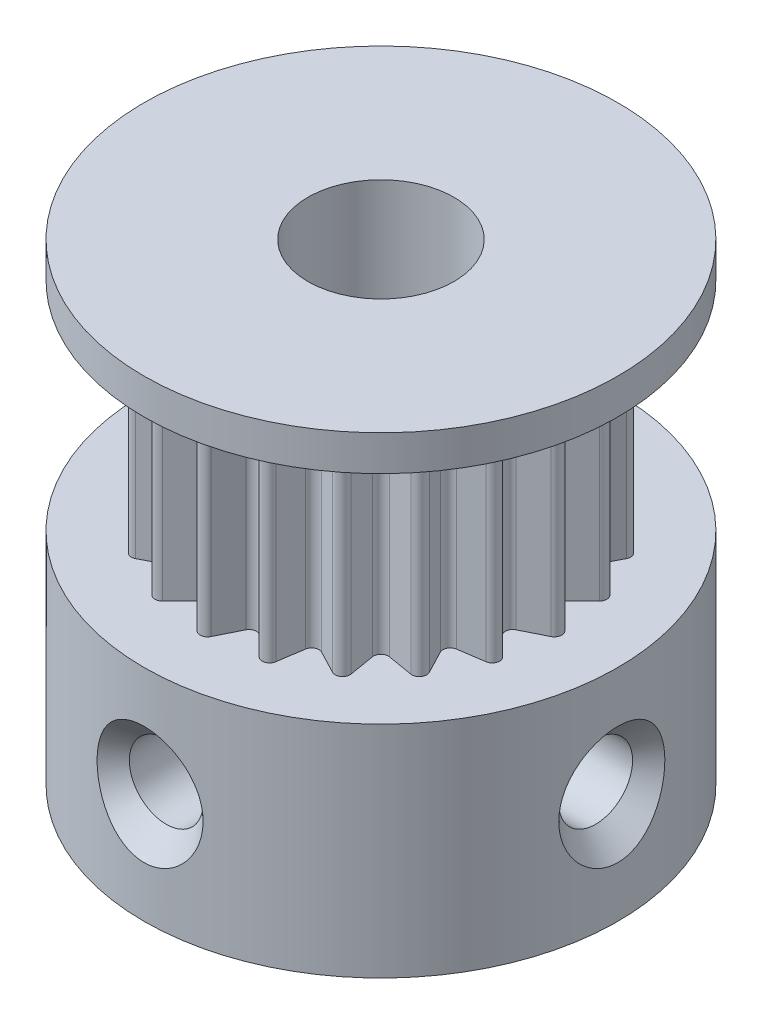
SolidWorks part; units mm, degrees
ref_plane "Front Plane" through (0, 0, 0) normal (0, 0, 1) x (1, 0, 0)
ref_plane "Top Plane" through (0, 0, 0) normal (0, 1, 0) x (1, 0, 0)
ref_plane "Right Plane" through (0, 0, 0) normal (1, 0, 0) x (0, 0, -1)
sketch "Sketch1" plane through (0, 0, 0) normal (0, 1, 0) x (1, 0, 0)
  circle A0 centre (0, 0) radius 8.025
  dimension "D1" = 16.05
extrude "Boss-Extrude1" add sketch "Sketch1" along normal blind 16
sketch "Sketch2" plane through (0, 16, 0) normal (0, 1, 0) x (1, 0, 0)
  line L0 (0.2238, 5.9865) -> (0.6171, 5.1973)
  line L1 (1.0192, 5.1336) -> (1.6371, 5.7627)
  line L2 (0, 0) -> (0, 6.125) construction
  line L3 (0.8408, 5.3088) -> (0.9582, 6.0496) construction
  line L4 (1.8927, 5.8252) -> (0, 0) construction
  line L5 (2.0627, 5.6244) -> (2.1929, 4.7522)
  line L6 (2.5557, 4.5674) -> (3.3378, 4.9747)
  line L7 (3.6998, 4.7117) -> (3.5541, 3.842)
  line L8 (3.842, 3.5541) -> (4.7117, 3.6998)
  line L9 (4.9747, 3.3378) -> (4.5674, 2.5557)
  line L10 (4.7522, 2.1929) -> (5.6244, 2.0627)
  line L11 (5.7627, 1.6371) -> (5.1336, 1.0192)
  line L12 (5.1973, 0.6171) -> (5.9865, 0.2238)
  line L13 (5.9865, -0.2238) -> (5.1973, -0.6171)
  line L14 (5.1336, -1.0192) -> (5.7627, -1.6371)
  line L15 (5.6244, -2.0627) -> (4.7522, -2.1929)
  line L16 (4.5674, -2.5557) -> (4.9747, -3.3378)
  line L17 (4.7117, -3.6998) -> (3.842, -3.5541)
  line L18 (3.5541, -3.842) -> (3.6998, -4.7117)
  line L19 (3.3378, -4.9747) -> (2.5557, -4.5674)
  line L20 (2.1929, -4.7522) -> (2.0627, -5.6244)
  line L21 (1.6371, -5.7627) -> (1.0192, -5.1336)
  line L22 (0.6171, -5.1973) -> (0.2238, -5.9865)
  line L23 (-0.2238, -5.9865) -> (-0.6171, -5.1973)
  line L24 (-1.0192, -5.1336) -> (-1.6371, -5.7627)
  line L25 (-2.0627, -5.6244) -> (-2.1929, -4.7522)
  line L26 (-2.5557, -4.5674) -> (-3.3378, -4.9747)
  line L27 (-3.6998, -4.7117) -> (-3.5541, -3.842)
  line L28 (-3.842, -3.5541) -> (-4.7117, -3.6998)
  line L29 (-4.9747, -3.3378) -> (-4.5674, -2.5557)
  line L30 (-4.7522, -2.1929) -> (-5.6244, -2.0627)
  line L31 (-5.7627, -1.6371) -> (-5.1336, -1.0192)
  line L32 (-5.1973, -0.6171) -> (-5.9865, -0.2238)
  line L33 (-5.9865, 0.2238) -> (-5.1973, 0.6171)
  line L34 (-5.1336, 1.0192) -> (-5.7627, 1.6371)
  line L35 (-5.6244, 2.0627) -> (-4.7522, 2.1929)
  line L36 (-4.5674, 2.5557) -> (-4.9747, 3.3378)
  line L37 (-4.7117, 3.6998) -> (-3.842, 3.5541)
  line L38 (-3.5541, 3.842) -> (-3.6998, 4.7117)
  line L39 (-3.3378, 4.9747) -> (-2.5557, 4.5674)
  line L40 (-2.1929, 4.7522) -> (-2.0627, 5.6244)
  line L41 (-1.6371, 5.7627) -> (-1.0192, 5.1336)
  line L42 (-0.6171, 5.1973) -> (-0.2238, 5.9865)
  line L43 (0, 0) -> (1.0192, 5.1336) construction
  line L44 (0, 0) -> (2.5557, 4.5674) construction
  circle A0 centre (0, 0) radius 6.125 construction
  arc A1 (0.2238, 5.9865) -> (0, 6.125) centre (0, 5.875) ccw
  arc A3 (0.6171, 5.1973) -> (1.0192, 5.1336) centre (0.8408, 5.3088) ccw
  arc A4 (1.6371, 5.7627) -> (1.8927, 5.8252) centre (1.8155, 5.5875) cw
  arc A5 (2.0627, 5.6244) -> (1.8927, 5.8252) centre (1.8155, 5.5875) ccw
  arc A6 (2.1929, 4.7522) -> (2.5557, 4.5674) centre (2.4402, 4.7892) ccw
  arc A7 (3.3378, 4.9747) -> (3.6002, 4.9552) centre (3.4532, 4.753) cw
  arc A8 (3.6998, 4.7117) -> (3.6002, 4.9552) centre (3.4532, 4.753) ccw
  arc A9 (3.5541, 3.842) -> (3.842, 3.5541) centre (3.8007, 3.8007) ccw
  arc A10 (4.7117, 3.6998) -> (4.9552, 3.6002) centre (4.753, 3.4532) cw
  arc A11 (4.9747, 3.3378) -> (4.9552, 3.6002) centre (4.753, 3.4532) ccw
  arc A12 (4.5674, 2.5557) -> (4.7522, 2.1929) centre (4.7892, 2.4402) ccw
  arc A13 (5.6244, 2.0627) -> (5.8252, 1.8927) centre (5.5875, 1.8155) cw
  arc A14 (5.7627, 1.6371) -> (5.8252, 1.8927) centre (5.5875, 1.8155) ccw
  arc A15 (5.1336, 1.0192) -> (5.1973, 0.6171) centre (5.3088, 0.8408) ccw
  arc A16 (5.9865, 0.2238) -> (6.125, 0) centre (5.875, 0) cw
  arc A17 (5.9865, -0.2238) -> (6.125, 0) centre (5.875, 0) ccw
  arc A18 (5.1973, -0.6171) -> (5.1336, -1.0192) centre (5.3088, -0.8408) ccw
  arc A19 (5.7627, -1.6371) -> (5.8252, -1.8927) centre (5.5875, -1.8155) cw
  arc A20 (5.6244, -2.0627) -> (5.8252, -1.8927) centre (5.5875, -1.8155) ccw
  arc A21 (4.7522, -2.1929) -> (4.5674, -2.5557) centre (4.7892, -2.4402) ccw
  arc A22 (4.9747, -3.3378) -> (4.9552, -3.6002) centre (4.753, -3.4532) cw
  arc A23 (4.7117, -3.6998) -> (4.9552, -3.6002) centre (4.753, -3.4532) ccw
  arc A24 (3.842, -3.5541) -> (3.5541, -3.842) centre (3.8007, -3.8007) ccw
  arc A25 (3.6998, -4.7117) -> (3.6002, -4.9552) centre (3.4532, -4.753) cw
  arc A26 (3.3378, -4.9747) -> (3.6002, -4.9552) centre (3.4532, -4.753) ccw
  arc A27 (2.5557, -4.5674) -> (2.1929, -4.7522) centre (2.4402, -4.7892) ccw
  arc A28 (2.0627, -5.6244) -> (1.8927, -5.8252) centre (1.8155, -5.5875) cw
  arc A29 (1.6371, -5.7627) -> (1.8927, -5.8252) centre (1.8155, -5.5875) ccw
  arc A30 (1.0192, -5.1336) -> (0.6171, -5.1973) centre (0.8408, -5.3088) ccw
  arc A31 (0.2238, -5.9865) -> (0, -6.125) centre (0, -5.875) cw
  arc A32 (-0.2238, -5.9865) -> (0, -6.125) centre (0, -5.875) ccw
  arc A33 (-0.6171, -5.1973) -> (-1.0192, -5.1336) centre (-0.8408, -5.3088) ccw
  arc A34 (-1.6371, -5.7627) -> (-1.8927, -5.8252) centre (-1.8155, -5.5875) cw
  arc A35 (-2.0627, -5.6244) -> (-1.8927, -5.8252) centre (-1.8155, -5.5875) ccw
  arc A36 (-2.1929, -4.7522) -> (-2.5557, -4.5674) centre (-2.4402, -4.7892) ccw
  arc A37 (-3.3378, -4.9747) -> (-3.6002, -4.9552) centre (-3.4532, -4.753) cw
  arc A38 (-3.6998, -4.7117) -> (-3.6002, -4.9552) centre (-3.4532, -4.753) ccw
  arc A39 (-3.5541, -3.842) -> (-3.842, -3.5541) centre (-3.8007, -3.8007) ccw
  arc A40 (-4.7117, -3.6998) -> (-4.9552, -3.6002) centre (-4.753, -3.4532) cw
  arc A41 (-4.9747, -3.3378) -> (-4.9552, -3.6002) centre (-4.753, -3.4532) ccw
  arc A42 (-4.5674, -2.5557) -> (-4.7522, -2.1929) centre (-4.7892, -2.4402) ccw
  arc A43 (-5.6244, -2.0627) -> (-5.8252, -1.8927) centre (-5.5875, -1.8155) cw
  arc A44 (-5.7627, -1.6371) -> (-5.8252, -1.8927) centre (-5.5875, -1.8155) ccw
  arc A45 (-5.1336, -1.0192) -> (-5.1973, -0.6171) centre (-5.3088, -0.8408) ccw
  arc A46 (-5.9865, -0.2238) -> (-6.125, 0) centre (-5.875, 0) cw
  arc A47 (-5.9865, 0.2238) -> (-6.125, 0) centre (-5.875, 0) ccw
  arc A48 (-5.1973, 0.6171) -> (-5.1336, 1.0192) centre (-5.3088, 0.8408) ccw
  arc A49 (-5.7627, 1.6371) -> (-5.8252, 1.8927) centre (-5.5875, 1.8155) cw
  arc A50 (-5.6244, 2.0627) -> (-5.8252, 1.8927) centre (-5.5875, 1.8155) ccw
  arc A51 (-4.7522, 2.1929) -> (-4.5674, 2.5557) centre (-4.7892, 2.4402) ccw
  arc A52 (-4.9747, 3.3378) -> (-4.9552, 3.6002) centre (-4.753, 3.4532) cw
  arc A53 (-4.7117, 3.6998) -> (-4.9552, 3.6002) centre (-4.753, 3.4532) ccw
  arc A54 (-3.842, 3.5541) -> (-3.5541, 3.842) centre (-3.8007, 3.8007) ccw
  arc A55 (-3.6998, 4.7117) -> (-3.6002, 4.9552) centre (-3.4532, 4.753) cw
  arc A56 (-3.3378, 4.9747) -> (-3.6002, 4.9552) centre (-3.4532, 4.753) ccw
  arc A57 (-2.5557, 4.5674) -> (-2.1929, 4.7522) centre (-2.4402, 4.7892) ccw
  arc A58 (-2.0627, 5.6244) -> (-1.8927, 5.8252) centre (-1.8155, 5.5875) cw
  arc A59 (-1.6371, 5.7627) -> (-1.8927, 5.8252) centre (-1.8155, 5.5875) ccw
  arc A60 (-1.0192, 5.1336) -> (-0.6171, 5.1973) centre (-0.8408, 5.3088) ccw
  arc A61 (-0.2238, 5.9865) -> (0, 6.125) centre (0, 5.875) cw
  circle A62 centre (0, 0) radius 8.025 construction
  circle A63 centre (0, 0) radius 8.025
  circle M4 centre (0, 0) radius 8.025
  dimension "D1" = 12.25
  dimension "D2" = 0.5
  dimension "D3" = 1
  dimension "D5" = 0.25
  dimension "D4" = 18
  dimension "D7" = 18
  dimension "D6" = 20
extrude "Cut-Extrude1" cut sketch "Sketch2" against normal blind 7.35 from offset 1.2 contours L42 A61 A1 L0 A3 L1 A4 A5 L5 A6 L6 A7 A8 L7 A9 L8 A10 A11 L9 A12 L10 A13 A14 L11 A15 L12 A16 A17 L13 A18 L14 A19 A20 L15 A21 L16 A22 A23 L17 A24 L18 A25 A26 L19 A27 L20 A28 A29 L21 M4 region at (-7.798, 16, 0) offset against normal yes
sketch "Sketch3" plane through (0, 16, 0) normal (0, 1, 0) x (1, 0, 0)
  circle A0 centre (0, 0) radius 2.475
  dimension "D1" = 4.95
extrude "Cut-Extrude2" cut sketch "Sketch3" against normal through all
hole_wizard "M3x0.5 Tapped Hole1" positions "3DSketch2" profile "Sketch4" tap size "M3x0.5" standard "ANSI Metric" end condition up to next
sketch3d "3DSketch2"
  line L0 (0, 0, 0) -> (0, 7.45, 0) construction
  line L1 (0, 7.45, 0) -> (0, 0, 0) construction
  line L2 (0, 3.725, 0) -> (0, 3.725, 8.025) construction
  point P9 (0, 3.725, 8.025)
sketch "Sketch4" plane through (0, 3.725, 8.025) normal (1, 0, 0) x (0, -1, 0)
  line L0 (0, 0) -> (0, 5.55)
  line L1 (0, 5.55) -> (1.25, 5.55)
  line L2 (1.25, 5.55) -> (1.25, 0.75)
  line L3 (1.25, 0.75) -> (2, 0)
  line L5 (2, 0) -> (0, 0)
  line L6 (-1.25, 0.75) -> (-2, 0) construction
  line L11 (0, -6.35) -> (0, 107.95) construction
  dimension "Thru Tap Drill Dia." = 2.5
  dimension "Thru Tap Drill Depth" = 5.55
  dimension "Near C'Sink Dia." = 4
  dimension "Near C'Sink Angle" = 90
cosmetic thread "Hole Thread1" parameters "D2"=3
pattern_circular "CirPattern1" count 2 over 90 about axis through (0, 16, 0) along (0, -1, 0) of "M3x0.5 Tapped Hole1" reverse direction yes
cosmetic thread "Hole Thread2" parameters "D2"=3
